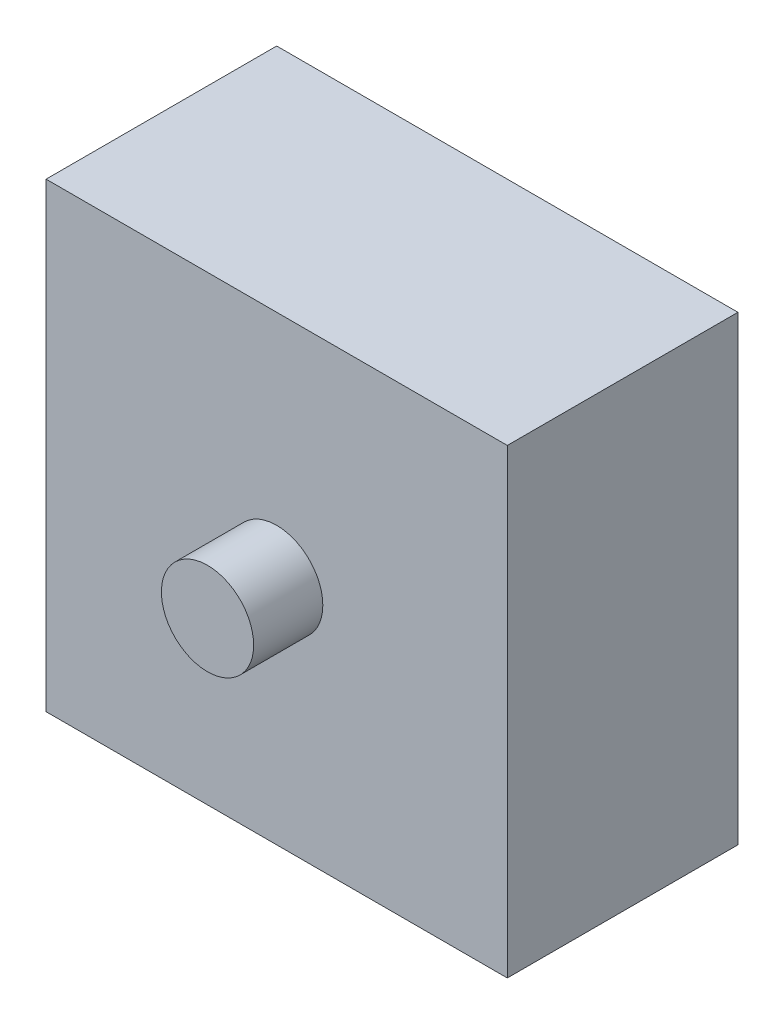
SolidWorks part; units mm, degrees
ref_plane "前视基准面" through (0, 0, 0) normal (0, 0, 1) x (1, 0, 0)
ref_plane "上视基准面" through (0, 0, 0) normal (0, 1, 0) x (1, 0, 0)
ref_plane "右视基准面" through (0, 0, 0) normal (1, 0, 0) x (0, 0, -1)
other "Configuration Table"
sketch "Sketch1" plane through (0, 0, 0) normal (0, 0, 1) x (1, 0, 0)
  line L1 (-100, -100) -> (100, -100)
  line L2 (-100, -100) -> (-100, 100)
  line L3 (-100, 100) -> (100, 100)
  line L4 (100, -100) -> (100, 100)
  line L5 (-100, -100) -> (100, 100) construction
  line L6 (-100, 100) -> (100, -100) construction
  point P0 (0, 0)
extrude "Boss-Extrude1" add sketch "Sketch1" along normal blind 100
ref_plane "Plane1" through (0, 0, 100) normal (0, 0, 1) x (1, 0, 0)
sketch "Sketch2" plane through (0, 0, 100) normal (0, 0, 1) x (1, 0, 0)
  circle A0 centre (0, 0) radius 20
extrude "Boss-Extrude2" add sketch "Sketch2" along normal blind 30
ref_plane "base_bottom_face" through (0, 0, 0) normal (0, 0, 1) x (1, 0, 0)
ref_plane "base_top_face" through (0, 0, 130) normal (0, 0, 1) x (1, 0, 0)
sketch3d "3DSketch1"
  line L0 (0, 0, 0) -> (0, 0, 1000) construction
ref_axis "base_top_axis" through (0, 0, 0) along (0, 0, 1)
